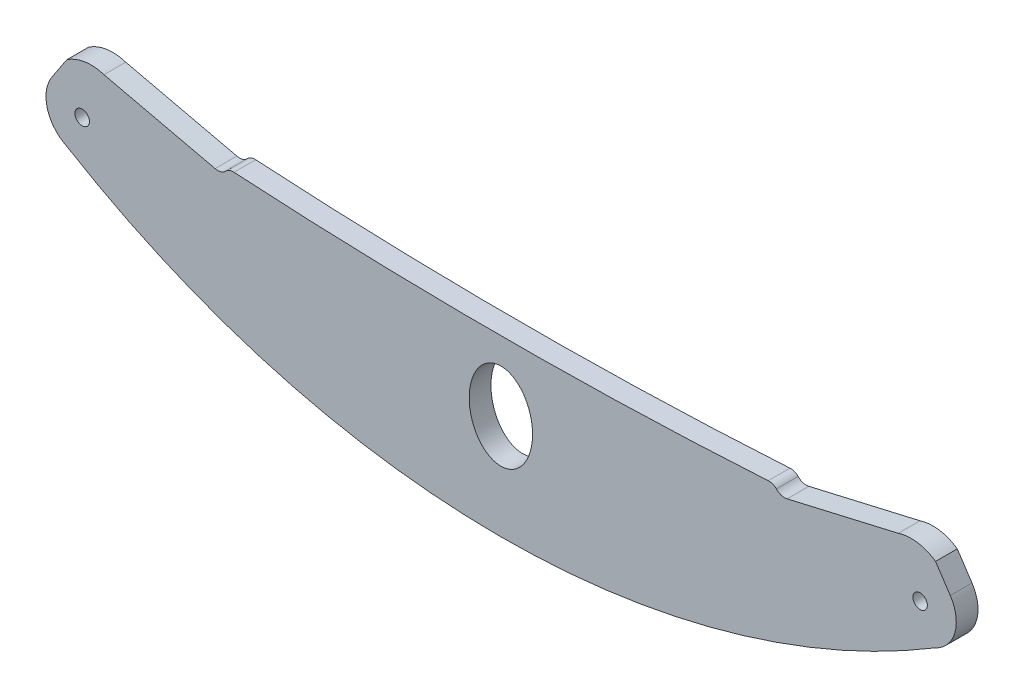
SolidWorks part; units mm, degrees
material "Perspex (TM) GS Acrylic Cast Sheet"
ref_plane "Front Plane" through (0, 0, 0) normal (0, 0, 1) x (1, 0, 0)
ref_plane "Top Plane" through (0, 0, 0) normal (0, 1, 0) x (1, 0, 0)
ref_plane "Right Plane" through (0, 0, 0) normal (1, 0, 0) x (0, 0, -1)
body saved out of another part "Stock-acrylic parts-1" [suppressed]
sketch "Sketch1" plane through (0, 0, 0) normal (0, 0, 1) x (1, 0, 0)
  line L1 (888.263, 101.3278) -> (897.0089, 101.3278) construction
  line L304 (954.7025, 110.9038) -> (952.6709, 113.9687)
  line L305 (947.5197, 114.7553) -> (932.1721, 111.2007)
  line L306 (853.1715, 111.1992) -> (837.8238, 114.7532)
  line L307 (832.6726, 113.9664) -> (830.6411, 110.9014)
  arc A0 (832.7255, 103.5937) -> (952.6184, 103.596) centre (892.67, 202.76) ccw
  circle A94 centre (834.8087, 108.1391) radius 1
  circle A95 centre (950.535, 108.1413) radius 1
  arc A98 (952.6184, 103.596) -> (954.7025, 110.9038) centre (950.535, 108.1413) ccw
  arc A99 (952.6709, 113.9687) -> (947.5197, 114.7553) centre (949.3098, 109.2178) ccw
  arc A100 (930.6861, 111.651) -> (932.1721, 111.2007) centre (931.8013, 112.6541) ccw
  arc A101 (930.6861, 111.651) -> (929.5576, 112.0619) centre (929.6871, 110.6626) ccw
  arc A102 (855.7695, 112.0619) -> (929.5576, 112.0619) centre (892.6636, 719.0984) ccw
  arc A103 (855.7695, 112.0619) -> (854.6575, 111.6496) centre (855.6565, 110.6612) ccw
  arc A104 (853.1715, 111.1992) -> (854.6575, 111.6496) centre (853.5422, 112.6526) ccw
  arc A105 (837.8238, 114.7532) -> (832.6726, 113.9664) centre (836.0339, 109.2156) ccw
  arc A106 (830.6411, 110.9014) -> (832.7255, 103.5937) centre (834.8087, 108.1391) ccw
  ellipse E0 centre (892.636, 101.3278) end of major axis (892.636, 95.3379) minor radius 4.3729
extrude "Boss-Extrude1" add sketch "Sketch1" along normal blind 3
